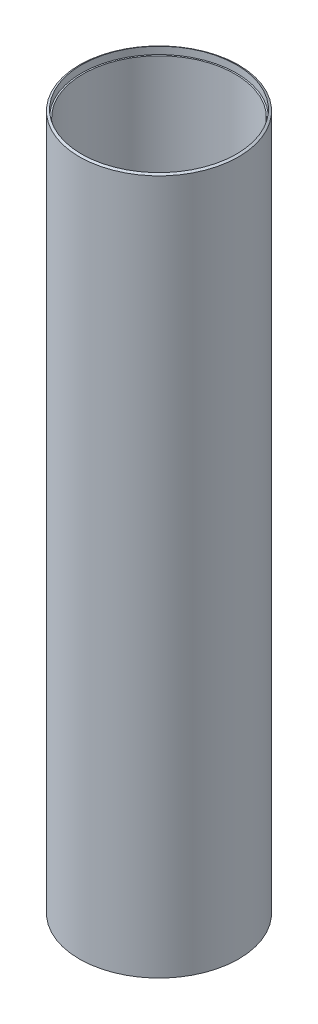
SolidWorks part; units mm, degrees
material "6061-T6 (SS)"
ref_plane "Front Plane" through (0, 0, 0) normal (0, 0, 1) x (1, 0, 0)
ref_plane "Top Plane" through (0, 0, 0) normal (0, 1, 0) x (1, 0, 0)
ref_plane "Right Plane" through (0, 0, 0) normal (1, 0, 0) x (0, 0, -1)
ref_axis "Axis1" through (0, 819.187, 0) along (0, -1, 0)
sketch "Sketch2" plane through (0, 0, 0) normal (0, 0, 1) x (1, 0, 0)
  line L0 (-69.85, 1.0999) -> (-69.85, 610.6999)
  line L1 (-67.945, 0) -> (-69.85, 1.0999)
  line L2 (-66.675, 6.35) -> (-66.675, 605.4497)
  line L3 (-67.945, 0) -> (-67.945, 6.35)
  line L4 (-69.85, 305.8999) -> (-65.786, 305.8999) construction
  line L5 (0, 819.187) -> (0, -55) construction
  line L6 (-67.945, 611.7997) -> (-69.85, 610.6999)
  line L7 (-67.945, 605.4497) -> (-66.675, 605.4497)
  line L8 (-67.945, 611.7997) -> (-67.945, 605.4497)
  line L9 (-67.945, 6.35) -> (-66.675, 6.35)
  line L13 (55, 0) -> (-55, 0) construction
  point P1 (-69.85, 305.8999)
  point P17 (-66.675, 305.8999)
  dimension "D2" = 3.175
  dimension "D3" = 304.8
  dimension "D4" = 69.85
  dimension "D6" = 60
  dimension "D10" = 1.27
  dimension "D11" = 6.35
revolve "Revolve1" add sketch "Sketch2" angle 360 about axis through (0, 819.187, 0) along (0, -1, 0)
